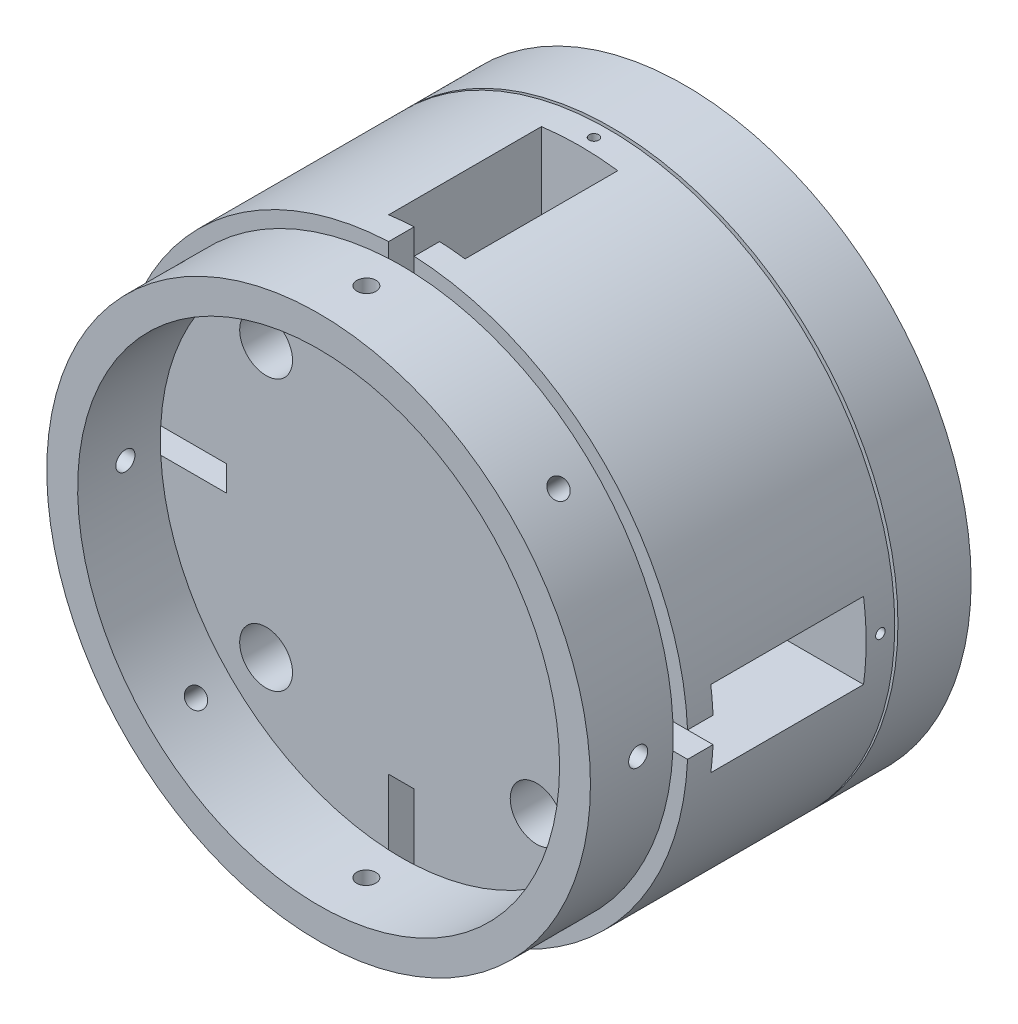
SolidWorks part; units mm, degrees
ref_plane "前视基准面" through (0, 0, 0) normal (0, 0, 1) x (1, 0, 0)
ref_plane "上视基准面" through (0, 0, 0) normal (0, 1, 0) x (1, 0, 0)
ref_plane "右视基准面" through (0, 0, 0) normal (1, 0, 0) x (0, 0, -1)
sketch "草图1" plane through (0, 0, 0) normal (0, 0, 1) x (1, 0, 0)
  circle A0 centre (0, 0) radius 45
extrude "凸台-拉伸1" add sketch "草图1" against normal blind 2.5
sketch "草图2" plane through (0, 0, 0) normal (0, 0, 1) x (1, 0, 0)
  line L0 (-25, 6.5) -> (-25, 2)
  line L1 (-6.5, 65) -> (6.5, 65)
  line L2 (-6.5, 65) -> (-6.5, 25)
  line L3 (-6.5, 25) -> (6.5, 25)
  line L4 (6.5, 65) -> (6.5, 25)
  line L5 (-6.5, 65) -> (6.5, 25) construction
  line L6 (-6.5, 25) -> (6.5, 65) construction
  line L7 (65, 6.5) -> (25, 6.5)
  line L8 (65, 6.5) -> (65, -6.5)
  line L9 (65, -6.5) -> (25, -6.5)
  line L10 (25, 6.5) -> (25, -6.5)
  line L11 (65, 6.5) -> (25, -6.5) construction
  line L12 (65, -6.5) -> (25, 6.5) construction
  line L13 (-6.5, -65) -> (6.5, -65)
  line L14 (-6.5, -65) -> (-6.5, -25)
  line L15 (-6.5, -25) -> (6.5, -25)
  line L16 (6.5, -65) -> (6.5, -25)
  line L17 (-6.5, -65) -> (6.5, -25) construction
  line L18 (-6.5, -25) -> (6.5, -65) construction
  line L19 (-65, -6.5) -> (-25, -6.5)
  line L20 (-65, -6.5) -> (-65, 6.5)
  line L21 (-65, 6.5) -> (-25, 6.5)
  line L22 (-25, -6.5) -> (-25, 6.5)
  line L23 (-65, -6.5) -> (-25, 6.5) construction
  line L24 (-65, 6.5) -> (-25, -6.5) construction
  line L25 (-67, -8.5) -> (-23, -8.5)
  line L26 (-67, -8.5) -> (-67, 8.5)
  line L27 (-67, 8.5) -> (-23, 8.5)
  line L28 (-23, -8.5) -> (-23, 8.5)
  line L29 (-67, -8.5) -> (-23, 8.5) construction
  line L30 (-67, 8.5) -> (-23, -8.5) construction
  line L31 (-8.5, 67) -> (8.5, 67)
  line L32 (-8.5, 67) -> (-8.5, 23)
  line L33 (-8.5, 23) -> (8.5, 23)
  line L34 (8.5, 67) -> (8.5, 23)
  line L35 (-8.5, 67) -> (8.5, 23) construction
  line L36 (-8.5, 23) -> (8.5, 67) construction
  line L37 (67, -8.5) -> (23, -8.5)
  line L38 (67, -8.5) -> (67, 8.5)
  line L39 (67, 8.5) -> (23, 8.5)
  line L40 (23, -8.5) -> (23, 8.5)
  line L41 (67, -8.5) -> (23, 8.5) construction
  line L42 (67, 8.5) -> (23, -8.5) construction
  line L43 (-8.5, -67) -> (8.5, -67)
  line L44 (-8.5, -67) -> (-8.5, -23)
  line L45 (-8.5, -23) -> (8.5, -23)
  line L46 (8.5, -67) -> (8.5, -23)
  line L47 (-8.5, -67) -> (8.5, -23) construction
  line L48 (-8.5, -23) -> (8.5, -67) construction
  line L49 (-45, -6.5) -> (-45, -2)
  line L50 (-6.5, 25) -> (-2, 25)
  line L51 (-45, -2) -> (-27.5, -2)
  line L52 (-45, -2) -> (-45, 2)
  line L53 (-45, 2) -> (-27.5, 2)
  line L54 (-27.5, -2) -> (-27.5, 2)
  line L55 (6.5, 45) -> (2, 45)
  line L56 (25, 6.5) -> (25, 2)
  line L57 (2, 45) -> (-2, 45)
  line L58 (2, 45) -> (2, 27.5)
  line L59 (2, 27.5) -> (-2, 27.5)
  line L60 (-2, 45) -> (-2, 27.5)
  line L61 (45, -6.5) -> (45, -2)
  line L62 (6.5, -25) -> (2, -25)
  line L63 (45, -2) -> (27.5, -2)
  line L64 (45, -2) -> (45, 2)
  line L65 (45, 2) -> (27.5, 2)
  line L66 (27.5, -2) -> (27.5, 2)
  line L67 (-6.5, -45) -> (-2, -44.9555)
  line L68 (-45, -6.5) -> (-25, -6.5)
  line L69 (-2, -44.9555) -> (2, -44.9555)
  line L70 (-2, -44.9555) -> (-2, -27.4555)
  line L71 (-2, -27.4555) -> (2, -27.4555)
  line L72 (2, -44.9555) -> (2, -27.4555)
  line L73 (-6.5, -25) -> (-6.5, -45)
  line L74 (-23, -8.5) -> (-45, -8.5)
  line L75 (-45, 8.5) -> (-23, 8.5)
  line L76 (-8.5, 45) -> (-8.5, 23)
  line L77 (8.5, 45) -> (8.5, 23)
  line L78 (45, 8.5) -> (23, 8.5)
  line L79 (45, -6.5) -> (25, -6.5)
  line L80 (8.5, -45) -> (8.5, -23)
  line L81 (45, -8.5) -> (23, -8.5)
  line L82 (34, -8.5) -> (8.5, -34)
  line L83 (-8.5, -45) -> (-8.5, -23)
  line L84 (-8.5, -34) -> (-34, -8.5)
  line L85 (-45, 8.5) -> (-23, 8.5)
  line L86 (-8.5, 45) -> (-8.5, 23)
  line L87 (-8.5, 34) -> (-34, 8.5)
  line L88 (8.5, 45) -> (8.5, 23)
  line L89 (45, 8.5) -> (23, 8.5)
  line L90 (34, 8.5) -> (8.5, 34)
  line L91 (-8.5, 23) -> (-3, 23)
  line L92 (8.5, 23) -> (3, 23)
  line L93 (-23, 8.5) -> (-23, 3)
  line L94 (-3, 23) -> (3, 23)
  line L95 (-3, 23) -> (-3, -23)
  line L96 (-3, -23) -> (3, -23)
  line L97 (3, 23) -> (3, -23)
  line L98 (-23, -8.5) -> (-23, -3)
  line L100 (-23, -3) -> (23, -3)
  line L101 (-23, -3) -> (-23, 3)
  line L102 (-23, 3) -> (23, 3)
  line L103 (23, -3) -> (23, 3)
  line L104 (-6, 65) -> (6, 65)
  line L105 (-6, 65) -> (-6, 25)
  line L106 (-6, 25) -> (6, 25)
  line L107 (6, 65) -> (6, 25)
  line L108 (-6, 65) -> (6, 25) construction
  line L109 (-6, 25) -> (6, 65) construction
  line L110 (65, 6) -> (25, 6)
  line L111 (65, 6) -> (65, -6)
  line L112 (65, -6) -> (25, -6)
  line L113 (25, 6) -> (25, -6)
  line L114 (65, 6) -> (25, -6) construction
  line L115 (65, -6) -> (25, 6) construction
  line L116 (-6, -65) -> (6, -65)
  line L117 (-6, -65) -> (-6, -25)
  line L118 (-6, -25) -> (6, -25)
  line L119 (6, -65) -> (6, -25)
  line L120 (-6, -65) -> (6, -25) construction
  line L121 (-6, -25) -> (6, -65) construction
  line L122 (-65, -6) -> (-25, -6)
  line L123 (-65, -6) -> (-65, 6)
  line L124 (-65, 6) -> (-25, 6)
  line L125 (-25, -6) -> (-25, 6)
  line L126 (-65, -6) -> (-25, 6) construction
  line L127 (-65, 6) -> (-25, -6) construction
  circle A0 centre (0, 0) radius 45 construction
  circle A1 centre (21.25, 21.25) radius 9
  circle A2 centre (21.25, 21.25) radius 4.05
  circle A3 centre (-21.25, 21.25) radius 9
  circle A4 centre (-21.25, 21.25) radius 4.05
  circle A5 centre (-21.25, -21.25) radius 9
  circle A6 centre (-21.25, -21.25) radius 4.05
  circle A7 centre (21.25, -21.25) radius 9
  circle A8 centre (21.25, -21.25) radius 4.05
  circle A9 centre (0, 0) radius 45
  point P0 (0, 45)
  point P7 (45, 0)
  point P12 (0, -45)
  point P17 (-45, 0)
  point P22 (-45, 0)
  point P27 (0, 45)
  point P32 (45, 0)
  point P37 (0, -45)
  point P102 (0, 45)
  point P107 (45, 0)
  point P112 (0, -45)
  point P117 (-45, 0)
  circle M39 centre (0, 0) radius 45
  dimension "D21" = 12
  dimension "D1" = 40
  dimension "D2" = 44
  dimension "D3" = 40
  dimension "D4" = 44
  dimension "D5" = 40
  dimension "D6" = 44
  dimension "D7" = 40
  dimension "D8" = 44
  dimension "D9" = 13
  dimension "D10" = 17
  dimension "D11" = 13
  dimension "D12" = 17
  dimension "D13" = 13
  dimension "D14" = 17
  dimension "D15" = 13
  dimension "D16" = 17
  dimension "D17" = 17.5
  dimension "D18" = 17.5
  dimension "D19" = 17.5
  dimension "D20" = 17.5
  dimension "D22" = 40
  dimension "D23" = 12
  dimension "D24" = 40
  dimension "D25" = 12
  dimension "D26" = 40
  dimension "D27" = 12
  dimension "D28" = 40
extrude "凸台-拉伸2" add sketch "草图2" along normal blind 26 contours L102 L95 L100 L97 | L102 L97 L100 L40 | L100 L95 L45 L97 | L102 L28 L100 L95 | L95 L102 L97 L33 | A8 L82 A7 | A8 L82 A7 | A6 L84 A5 | A6 L84 A5 | A4 L87 A3 | A4 L87 A3 | A2 L90 A1 | A2 L90 A1 | L112 L10 L9 M39 | L110 L7 L10 M39 | L107 L3 L4 M39 | L124 L0 L21 M39 | L122 L19 L22 M39 | L117 L15 L14 M39 | L119 L16 L62 M39 | L40 L81 L37 L9 L10 L56 L7 L39 L89 M39 | L105 L2 L3 M39 | L34 L4 L3 L50 L2 L32 L86 L33 L88 M39 | L25 L74 L28 L85 L27 L21 L0 L22 L19 M39 | L46 L80 L45 L83 L44 L14 L15 L62 L16 M39 region at (-34.764, 6.7743, 0) region at (-34.7818, 6.2499, 0) region at (-34.7818, -6.2499, 0) region at (-7.4562, 44.0998, 0) region at (-24.3282, 24.3282, 0) region at (-18.1718, 18.1718, 0) region at (-6.2499, 34.7818, 0) region at (-13, 0, 0) region at (0, 0, 0) region at (0, 13, 0) region at (-8.2257, -39.095, 0) region at (0, -13, 0) region at (13, 0, 0) region at (-18.1718, -18.1718, 0) region at (-24.3282, -24.3282, 0) region at (-6.2499, -34.7818, 0) region at (23.2743, 5.75, 0) region at (6.2499, 34.7818, 0) region at (24.3282, 24.3282, 0) region at (18.1718, 18.1718, 0) region at (34.7818, 6.2499, 0) region at (6.2499, -34.7818, 0) region at (18.1718, -18.1718, 0) region at (24.3282, -24.3282, 0) region at (34.7818, -6.2499, 0)
ref_plane "基准面1" through (0, 0, 24) normal (0, 0, 1) x (1, 0, 0)
sketch "草图6" plane through (0, 0, 24) normal (0, 0, 1) x (1, 0, 0)
  circle A0 centre (0, 0) radius 42.7
  circle A1 centre (0, 0) radius 37.85
extrude "切除-拉伸4" cut sketch "草图2<5>" against normal blind 10 and the other way blind 30 contours L90 A2 | L90 A2 | L87 A4 | L87 A4 | L84 A6 | L84 A6 | L82 A8 | L82 A8 region at (-22.4654, 22.4654, 0) region at (-20.0346, 20.0346, 0) region at (-20.0346, -20.0346, 0) region at (-22.4654, -22.4654, 0) region at (22.4654, 22.4654, 0) region at (20.0346, 20.0346, 0) region at (20.0346, -20.0346, 0) region at (22.4654, -22.4654, 0)
sketch "草图2<5>" plane through (0, 0, 0) normal (0, 0, 1) x (1, 0, 0) same geometry as "草图2"
sketch "草图11" plane through (0, 0, -2.5) normal (0, 0, -1) x (-1, 0, 0)
  circle A0 centre (0, 0) radius 42.7
  circle A1 centre (0, 0) radius 37.85
extrude "凸台-拉伸5" add sketch "草图11" along normal blind 11
sketch "草图12" plane through (0, 0, 0) normal (0, 1, 0) x (1, 0, 0)
  circle A0 centre (0, 8.75) radius 1.5
extrude "切除-拉伸5" cut sketch "草图12" against normal blind 50 and the other way blind 50
sketch "草图13" plane through (0, 0, 0) normal (1, 0, 0) x (0, 0, -1)
  circle A0 centre (8.75, 0) radius 1.5
extrude "切除-拉伸6" cut sketch "草图13" against normal blind 50 and the other way blind 50
sketch "草图14" plane through (0, 0, 0) normal (1, 0, 0) x (0, 0, -1)
  line L0 (15.1195, 0) -> (-35.6195, 0)
ref_plane "基准面2" through (0, 0, 0) normal (0.7071, 0.7071, 0) x (0, 0, 1)
ref_plane "基准面3" through (0, 0, 0) normal (-0.7071, 0.7071, 0) x (0, 0, 1)
sketch "草图18" plane through (0, 0, 0) normal (0.7071, 0.7071, 0) x (0, 0, 1)
  line L2 (-15.1195, 0) -> (35.6195, 0) construction
  circle A0 centre (-8.75, 0) radius 1.5
extrude "切除-拉伸7" cut sketch "草图18" against normal blind 50 and the other way blind 50
sketch "草图19" plane through (0, 0, 0) normal (-0.7071, 0.7071, 0) x (0, 0, 1)
  line L0 (-13.5, 0) -> (-8.75, 0)
  line L1 (-13.5, 42.7) -> (-13.5, -42.7) construction
  line L2 (-15.1195, 0) -> (35.6195, 0) construction
  circle A0 centre (-8.75, 0) radius 1.5
extrude "切除-拉伸8" cut sketch "草图19" against normal blind 50 and the other way blind 50 contours A0
sketch "草图24" plane through (0, 0, 0) normal (0, 0, 1) x (1, 0, 0)
  line L0 (-6, 44.5982) -> (-6, 25)
  line L1 (-6, 25) -> (6, 25)
  line L2 (6, 25) -> (6, 44.5982)
  line L3 (44.5982, 6) -> (25, 6)
  line L4 (25, 6) -> (25, -6)
  line L5 (25, -6) -> (44.5982, -6)
  line L6 (6, -44.5982) -> (6, -25)
  line L7 (6, -25) -> (-6, -25)
  line L8 (-6, -25) -> (-6, -44.5982)
  line L9 (-44.5982, -6) -> (-25, -6)
  line L10 (-25, -6) -> (-25, 6)
  line L11 (-25, 6) -> (-44.5982, 6)
  arc A0 (-44.5982, 6) -> (-44.5982, -6) centre (0, 0) ccw
  arc A1 (6, 44.5982) -> (-6, 44.5982) centre (0, 0) ccw
  arc A2 (44.5982, -6) -> (44.5982, 6) centre (0, 0) ccw
  arc A3 (-6, -44.5982) -> (6, -44.5982) centre (0, 0) ccw
extrude "凸台-拉伸7" add sketch "草图24" along normal blind 2
sketch "草图26" plane through (0, 0, 0) normal (0, 0, 1) x (1, 0, 0)
  line L0 (-8.5, 42.1515) -> (-8.5, 44.1899)
  line L1 (-8.5, 44.1899) -> (-8.5, 23) construction
  line L2 (8.5, 42.1515) -> (8.5, 44.1899)
  line L3 (42.1515, 8.5) -> (44.1899, 8.5)
  line L4 (44.1899, 8.5) -> (23, 8.5) construction
  line L5 (42.1515, -8.5) -> (44.1899, -8.5)
  line L6 (8.5, -42.1515) -> (8.5, -44.1899)
  line L7 (8.5, -44.1899) -> (8.5, -23) construction
  line L8 (-8.5, -42.1515) -> (-8.5, -44.1899)
  line L9 (-42.1515, -8.5) -> (-44.1899, -8.5)
  line L10 (-44.1899, -8.5) -> (-23, -8.5) construction
  line L11 (-42.1515, 8.5) -> (-44.1899, 8.5)
  line L12 (-44.1899, 8.5) -> (-23, 8.5) construction
  arc A0 (-44.1899, -8.5) -> (-8.5, -44.1899) centre (0, 0) ccw
  arc A1 (-42.1515, -8.5) -> (-8.5, -42.1515) centre (0, 0) ccw
  arc A2 (-8.5, 42.1515) -> (-42.1515, 8.5) centre (0, 0) ccw
  arc A3 (-8.5, 44.1899) -> (-44.1899, 8.5) centre (0, 0) ccw
  arc A4 (44.1899, 8.5) -> (8.5, 44.1899) centre (0, 0) ccw
  arc A5 (42.1515, 8.5) -> (8.5, 42.1515) centre (0, 0) ccw
  arc A6 (8.5, -42.1515) -> (42.1515, -8.5) centre (0, 0) ccw
  arc A7 (8.5, -44.1899) -> (44.1899, -8.5) centre (0, 0) ccw
extrude "凸台-拉伸8" add sketch "草图26" along normal blind 30
sketch "草图29" plane through (0, 0, 26) normal (0, 0, 1) x (1, 0, 0)
  circle A0 centre (0, 0) radius 45.1498
extrude "凸台-拉伸9" add sketch "草图29" along normal blind 4
sketch "草图30" plane through (0, 0, 30) normal (0, 0, 1) x (1, 0, 0)
  circle A0 centre (0, 0) radius 42.7
  circle A1 centre (0, 0) radius 37.85
extrude "凸台-拉伸10" add sketch "草图30" along normal blind 11
sketch "草图31" plane through (0, 0, 30) normal (0, 0, 1) x (1, 0, 0)
  circle A0 centre (0, 0) radius 45
  circle A1 centre (0, 0) radius 47.0524
extrude "切除-拉伸9" cut sketch "草图31" against normal blind 40
sketch "草图32" plane through (0, 0, 30) normal (0, 0, 1) x (1, 0, 0)
  line L1 (-2, 27.5) -> (2, 27.5)
  line L2 (-2, 27.5) -> (-2, 62.5)
  line L3 (-2, 62.5) -> (2, 62.5)
  line L4 (2, 27.5) -> (2, 62.5)
  line L5 (-2, 27.5) -> (2, 62.5) construction
  line L6 (-2, 62.5) -> (2, 27.5) construction
  line L7 (62.5, -2) -> (27.5, -2)
  line L8 (62.5, -2) -> (62.5, 2)
  line L9 (62.5, 2) -> (27.5, 2)
  line L10 (27.5, -2) -> (27.5, 2)
  line L11 (62.5, -2) -> (27.5, 2) construction
  line L12 (62.5, 2) -> (27.5, -2) construction
  line L13 (-2, -62.5) -> (2, -62.5)
  line L14 (-2, -62.5) -> (-2, -27.5)
  line L15 (-2, -27.5) -> (2, -27.5)
  line L16 (2, -62.5) -> (2, -27.5)
  line L17 (-2, -62.5) -> (2, -27.5) construction
  line L18 (-2, -27.5) -> (2, -62.5) construction
  line L19 (-62.5, -2) -> (-27.5, -2)
  line L20 (-62.5, -2) -> (-62.5, 2)
  line L21 (-62.5, 2) -> (-27.5, 2)
  line L22 (-27.5, -2) -> (-27.5, 2)
  line L23 (-62.5, -2) -> (-27.5, 2) construction
  line L24 (-62.5, 2) -> (-27.5, -2) construction
  arc A0 (-44.9555, 2) -> (-44.9555, -2) centre (0, 0) ccw
  arc A2 (2, 44.9555) -> (-2, 44.9555) centre (0, 0) ccw
  arc A3 (44.9555, -2) -> (44.9555, 2) centre (0, 0) ccw
  arc A4 (-2, -44.9555) -> (2, -44.9555) centre (0, 0) ccw
  point P3 (0, 45)
  point P8 (45, 0)
  point P13 (0, -45)
  point P18 (-45, 0)
  circle M9 centre (0, 0) radius 42.7
  circle M10 centre (0, 0) radius 45
  dimension "D1" = 4
  dimension "D2" = 35
  dimension "D3" = 35
  dimension "D4" = 4
  dimension "D5" = 35
  dimension "D6" = 4
  dimension "D7" = 35
  dimension "D8" = 4
extrude "切除-拉伸10" cut sketch "草图32" against normal blind 4 contours L19 L22 L21 M9 | L1 L4 L2 M9 | L10 L7 L9 M9 | L16 L15 L14 M9 | L4 L2 M9 M10 | L9 L7 M10 M9 | L16 L14 M10 M9 | L21 L19 M10 M9 region at (0, 35.0922, 30) region at (0, 43.8348, 30) region at (-43.8348, 0, 30) region at (-35.0922, 0, 30) region at (35.0922, 0, 30) region at (43.8348, 0, 30) region at (0, -43.8348, 30) region at (0, -35.0922, 30)
sketch "草图35" plane through (0, 0, 0) normal (1, 0, 0) x (0, 0, -1)
  line L0 (-30, 0) -> (-41, 0)
  line L1 (-30, -2) -> (-30, 2) construction
  line L2 (-41, 42.7) -> (-41, -42.7) construction
  circle A0 centre (-35.5, 0) radius 1.5
extrude "切除-拉伸11" cut sketch "草图35" against normal blind 50 and the other way blind 50 contours L0 A0 | L0 A0 region at (0, -0.6366, 35.5) region at (0, 0.6366, 35.5)
sketch "草图36" plane through (0, 0, 0) normal (0, 1, 0) x (1, 0, 0)
  line L0 (0, -41) -> (0, -30)
  line L1 (-42.7, -41) -> (42.7, -41) construction
  line L2 (0, 15.1195) -> (0, -35.6195) construction
  circle A0 centre (0, -35.5) radius 1.5
extrude "切除-拉伸12" cut sketch "草图36" against normal blind 50 and the other way blind 50 contours L0 A0 | L0 A0 region at (-0.6366, 0, 35.5) region at (0.6366, 0, 35.5)
sketch "草图37" plane through (0, 0, 0) normal (0.7071, 0.7071, 0) x (0, 0, 1)
  line L0 (30, 0) -> (41, 0)
  line L1 (30, -30.3741) -> (30, 30.3741) construction
  line L2 (41, -42.7) -> (41, 42.7) construction
  circle A0 centre (35.5, 0) radius 1.5
extrude "切除-拉伸13" cut sketch "草图37" against normal blind 50 and the other way blind 50 contours L0 A0 | L0 A0 region at (0.4502, -0.4502, 35.5) region at (-0.4502, 0.4502, 35.5)
sketch "草图38" plane through (0, 0, 0) normal (-0.7071, 0.7071, 0) x (0, 0, 1)
  line L0 (41, 0) -> (30, 0)
  line L1 (41, -42.7) -> (41, 42.7) construction
  line L2 (30, -28.7461) -> (30, 28.7461) construction
  circle A0 centre (35.5, 0) radius 1.5
extrude "切除-拉伸14" cut sketch "草图38" against normal blind 50 and the other way blind 50 contours L0 A0 | L0 A0 region at (-0.4502, -0.4502, 35.5) region at (0.4502, 0.4502, 35.5)
sketch "草图39" plane through (0, 0, -13.5) normal (0, 0, -1) x (-1, 0, 0)
  circle A0 centre (0, 0) radius 42.7
  circle A1 centre (0, 0) radius 37.85
extrude "凸台-拉伸11" add sketch "草图39" along normal blind 1
sketch "草图40" plane through (0, 0, 0) normal (1, 0, 0) x (0, 0, -1)
  line L0 (-2, 0) -> (0.25, 0)
  line L1 (-2, 6) -> (-2, -6) construction
  line L2 (15.1195, 0) -> (-35.6195, 0) construction
  line L3 (-26, 0) -> (-28.25, 0)
  line L4 (-26, -2) -> (-26, 2) construction
  circle A0 centre (0.25, 0) radius 1
  circle A1 centre (-28.25, 0) radius 1
ref_plane "基准面4" through (45, 0, 0) normal (1, 0, 0) x (0, 0, -1)
sketch "草图41" plane through (45, 0, 0) normal (1, 0, 0) x (0, 0, -1)
  circle A0 centre (0.25, 0) radius 0.75
  circle A1 centre (-28.25, 0) radius 1
extrude "切除-拉伸15" cut sketch "草图41" against normal blind 8
ref_plane "基准面5" through (-45, 0, 0) normal (-1, 0, 0) x (0, 0, 1)
sketch "草图42" plane through (-45, 0, 0) normal (-1, 0, 0) x (0, 0, 1)
  circle A0 centre (-0.25, 0) radius 0.75
extrude "切除-拉伸21" cut sketch "草图42" against normal blind 8
ref_plane "基准面6" through (0, 45, 0) normal (0, 1, 0) x (1, 0, 0)
sketch "草图43" plane through (0, 45, 0) normal (0, 1, 0) x (1, 0, 0)
  line L0 (0, -2) -> (0, 0.25)
  line L1 (-6, -2) -> (6, -2) construction
  line L2 (0, 15.1195) -> (0, -35.6195) construction
  circle A0 centre (0, 0.25) radius 0.75
extrude "切除-拉伸22" cut sketch "草图43" against normal blind 8 contours A0 region at (0.5153, 45, 0.2653)
ref_plane "基准面8" through (0, -45, 0) normal (0, -1, 0) x (-1, 0, 0)
sketch "草图44" plane through (0, -45, 0) normal (0, -1, 0) x (-1, 0, 0)
  line L0 (0, -2) -> (0, 0.25)
  line L1 (-6, -2) -> (6, -2) construction
  line L2 (0, 15.1195) -> (0, -35.6195) construction
  circle A0 centre (0, 0.25) radius 0.75
extrude "切除-拉伸23" cut sketch "草图44" against normal blind 8 contours A0 region at (-0.5153, -45, 0.2653)
sketch "草图45" plane through (0, 0, -2.5) normal (0, 0, -1) x (-1, 0, 0)
  line L0 (-21.25, 21.25) -> (-12.9627, 29.5373)
  circle A0 centre (-12.9627, 29.5373) radius 5
  circle A1 centre (-12.9627, 29.5373) radius 6
  circle M6 centre (0, 0) radius 37.85
extrude "凸台-拉伸12" add sketch "草图45" against normal blind 32 contours A1 A0 M6 region at (18.7923, 29.4478, -2.5)
sketch "草图47" plane through (0, 0, -2.5) normal (0, 0, -1) x (-1, 0, 0)
  circle A0 centre (-12.9627, 29.5373) radius 5
extrude "切除-拉伸24" cut sketch "草图47" against normal blind 35
sketch "草图49" plane through (0, 0, -2.5) normal (0, 0, -1) x (-1, 0, 0)
  circle A0 centre (-21.25, 21.25) radius 4.05
  circle A1 centre (-21.25, -21.25) radius 4.05
  circle A2 centre (21.25, -21.25) radius 4.05
  circle A3 centre (21.25, 21.25) radius 4.05
extrude "切除-拉伸25" cut sketch "草图49" against normal blind 35
sketch "草图50" plane through (0, 0, -2.5) normal (0, 0, -1) x (-1, 0, 0)
  circle A0 centre (-21.25, 21.25) radius 4.15
  circle A1 centre (21.25, 21.25) radius 4.15
  circle A2 centre (-21.25, -21.25) radius 4.15
  circle A3 centre (21.25, -21.25) radius 4.15
extrude "切除-拉伸26" cut sketch "草图50" against normal blind 50
sketch "草图54" plane through (0, 0, 41) normal (0, 0, 1) x (1, 0, 0)
  circle A0 centre (0, 0) radius 37.85
  circle A1 centre (0, 0) radius 42.7
extrude "凸台-拉伸13" add sketch "草图54" along normal blind 2
sketch "草图55" plane through (0, 0, -14.5) normal (0, 0, -1) x (-1, 0, 0)
  circle A0 centre (0, 0) radius 45
  circle A1 centre (0, 0) radius 43.2
extrude "凸台-拉伸14" add sketch "草图55" against normal blind 11.5 separate body
